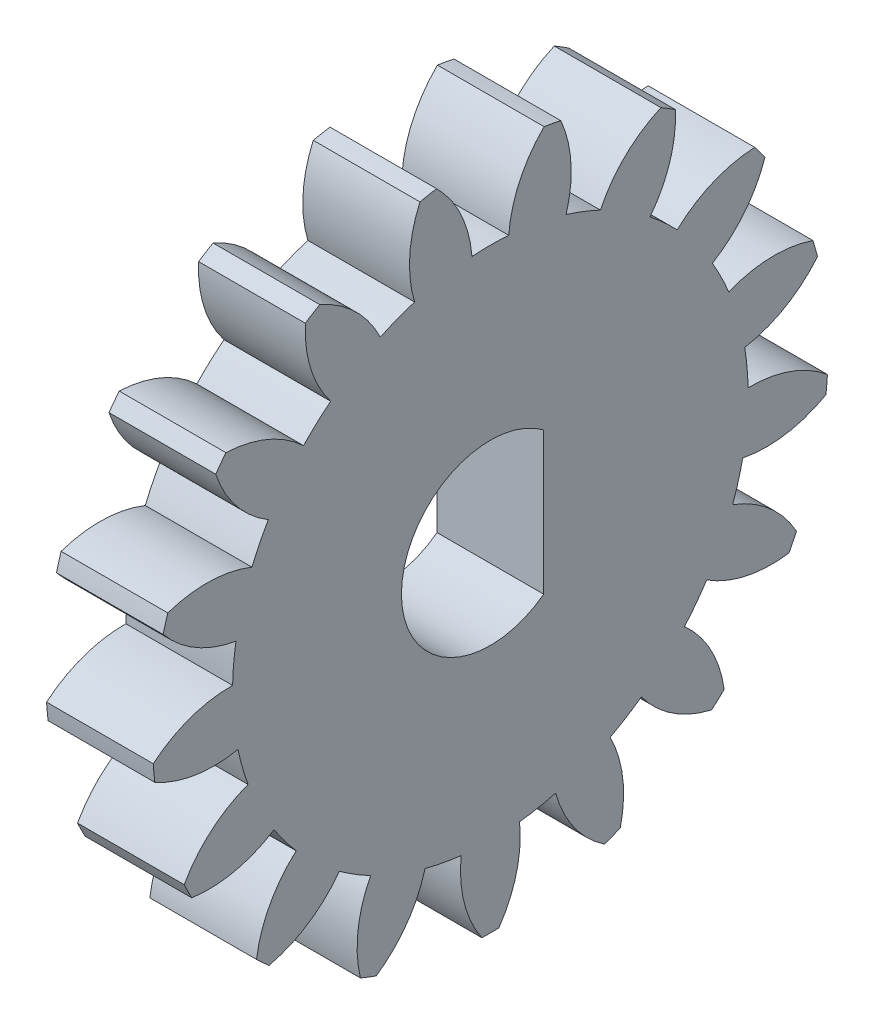
SolidWorks part; units mm, degrees
ref_plane "Plane1" through (0, 0, 0) normal (0, 0, 1) x (1, 0, 0)
ref_plane "Plane2" through (0, 0, 0) normal (0, 1, 0) x (1, 0, 0)
ref_plane "Plane3" through (0, 0, 0) normal (1, 0, 0) x (0, 0, -1)
other "Configuration Table"
sketch "HoldingSke" plane through (0, 0, 0) normal (0, 1, 0) x (1, 0, 0)
  line L0 (0, 0) -> (0.9563, -0.2924)
  line L1 (-15, 0) -> (100, 0) construction
  line L2 (0, 0) -> (-2.1039, 2.3779)
  line L3 (0, 0) -> (-11.863, 4.5341)
  line L4 (0, 0) -> (8.2586, 2.5249)
  line L5 (0, 0) -> (-46.8476, -17.4728)
  line L6 (0, 0) -> (-2.4869, -1.6779)
  line L7 (-2.1039, 2.3779) -> (8.6586, 51.2059)
  line L8 (-76.2, 54.61) -> (-75.3, 54.61)
  line L9 (-71.009, 38.7566) -> (-53.1078, 45.2721)
  line L10 (-76.2, 71.12) -> (104.1128, 71.12)
  line L11 (0, 0) -> (-3, 0)
  line L12 (-76.2, 101.6) -> (-76.162, 101.6)
  line L13 (24.9733, 27.94) -> (52.9518, 28.4284)
  line L14 (24.9733, 27.94) -> (24.9743, 27.94)
  line L15 (24.9733, 27.94) -> (100.4006, 29.5858)
  line L16 (-63.627, -1) -> (-12.827, -1)
  circle A0 centre (0, 0) radius 2.5
  circle A1 centre (0, 0) radius 7.249
  circle A2 centre (0, 0) radius 37.5
  circle A3 centre (0, 0) radius 2.5
  dimension "Num_teeth" = 17
  dimension "Pitch_radius" = 180.3128
  dimension "Width" = 3
  dimension "Thickness" = 3
sketch "BasProSke" plane through (0, 0, 0) normal (0, 1, 0) x (1, 0, 0)
  line L0 (-10, 0) -> (60, 0) construction
  line L1 (0, 0) -> (0, 9.5)
  line L2 (0, 0) -> (3, 0)
  line L3 (3, 0) -> (3, 9.5)
  line L4 (3, 9.5) -> (0, 9.5)
  dimension "Thickness" = 3
  dimension "Diameter" = 19
revolve "Base-Revolve" add sketch "BasProSke" angle 360 about L0
sketch "TooCutSke" plane through (0, 0, 0) normal (1, 0, 0) x (0, 0, -1)
  line L1 (0, 0) -> (0, 107) construction
  line L2 (0, 0) -> (-0.8507, 8.4573) construction
  line L3 (0, 0) -> (-3.1126, 16.6509) construction
  line L4 (-0.8507, 8.4573) -> (-1.5563, 8.3254) construction
  arc A0 (0.5169, 7.2306) -> (-0.5169, 7.2306) centre (0, 0) ccw
  arc A1 (1.5331, 9.4012) -> (-1.5331, 9.4012) centre (0, 0) ccw
  circle A2 centre (0, 0) radius 8.5 construction
  circle A3 centre (0, 0) radius 7.9874 construction
  arc A4 (-0.5169, 7.2306) -> (-1.5331, 9.4012) centre (-3.9066, 6.9668) ccw
  arc A5 (1.5331, 9.4012) -> (0.5169, 7.2306) centre (3.9066, 6.9668) ccw
extrude "ToothCut" cut sketch "TooCutSke" along normal through all
fillet "Breaks" [suppressed] radius 0.02 tangent propagation no
fillet "RootFillets" [suppressed] radius 0.251
pattern_circular "TeethCuts" count 17 every 21.176 about axis through (-10, 0, 0) along (1, 0, 0) of "ToothCut", "RootFillets", "Breaks"
sketch "HubNeaOneSke" plane through (0, 0, 0) normal (-1, 0, 0) x (0, 0, 1)
  circle A0 centre (0, 0) radius 7.249
  dimension "Diameter" = 14.498
extrude "HubNearOne" [suppressed] add sketch "HubNeaOneSke" along normal blind 47.0001
sketch "HubNeaBotSke" plane through (0, 0, 0) normal (-1, 0, 0) x (0, 0, 1)
  circle A0 centre (0, 0) radius 7.249
  dimension "Diameter" = 14.498
extrude "HubNearBoth" [suppressed] add sketch "HubNeaBotSke" along normal blind 23.5
ref_plane "FarPln" through (3, 0, 0) normal (1, 0, 0) x (0, 0, -1)
sketch "HubFarSke" plane through (3, 0, 0) normal (1, 0, 0) x (0, 0, -1)
  circle A0 centre (0, 0) radius 7.249
  dimension "Diameter" = 14.498
extrude "HubFar" [suppressed] add sketch "HubFarSke" along normal blind 23.5
sketch "BorSke" plane through (0, 0, 0) normal (1, 0, 0) x (0, 0, -1)
  circle A0 centre (0, 0) radius 2.5
  dimension "Diameter" = 5
extrude "Bore" cut sketch "BorSke" along normal mid plane 100.0001
sketch "KeySke" plane through (0, 0, 0) normal (1, 0, 0) x (0, 0, -1)
  line L0 (-1, 0) -> (-1, 3.4)
  line L1 (-1, 3.4) -> (1, 3.4)
  line L2 (1, 3.4) -> (1, 0)
  line L3 (0, 0) -> (0, 34) construction
  line L4 (-1, 0) -> (1, 0)
  dimension "Width" = 2
extrude "Keyway" [suppressed] cut sketch "KeySke" along normal mid plane 100.0001
pattern_circular "Keyway2" [suppressed] count 2 every 90 about axis through (-10, 0, 0) along (1, 0, 0) reverse direction yes
sketch "草图1" plane through (3, 0, 0) normal (1, 0, 0) x (0, 0, -1)
  line L0 (1.5, 2) -> (1.5, -2)
  arc A0 (1.5, -2) -> (1.5, 2) centre (0, 0) ccw
  dimension "D1" = 1.5
extrude "凸台-拉伸1" add sketch "草图1" against normal blind 3
equation "' \"Module@HoldingSke\" = 6.35"
equation "' \"Num_teeth@HoldingSke\" = 12"
equation "' \"Ap@HoldingSke\" =  20"
equation "' \"Ap@HoldingSke\" = 20"
equation "' \"Width@HoldingSke\" = 0.5 * 25.4"
equation "' \"Hub_dia@HoldingSke\"= 1 * 25.4"
equation "' \"Hub_dia@HoldingSke\" = 1 * 25.4"
equation "' \"Overall_len@HoldingSke\" = 1.0 * 25.4"
equation "' \"Bore@HoldingSke\" = 0.75 * 25.4"
equation "' \"T_dim@HoldingSke\" = 0.1 * 25.4"
equation "' \"Width@KeySke\" = 0.25 * 25.4"
equation "' \"Show_teeth@HoldingSke\" = 13"
equation "' \"Backlash@HoldingSke\" = 0.009 * 25.4"
equation "' \"Addendum_fac@HoldingSke\" = 1.0"
equation "' \"Dedendum_fac@HoldingSke\" = 1.25"
equation "' \"Dedendum_add@HoldingSke\" = 0.00005 * 25.4"
equation "' \"Clearance_fac@HoldingSke\" = 0.25"
equation "\"Pitch@HoldingSke\" = 1 / \"Module@HoldingSke\""
equation "\"Overcut_dia@TooCutSke\" = (\"Num_teeth@HoldingSke\" + 2 * \"Addendum_fac@HoldingSke\") / \"Pitch@HoldingSke\" + 0.002 * 25.4"
equation "\"Pitch_dia@TooCutSke\" = \"Num_teeth@HoldingSke\" / \"Pitch@HoldingSke\""
equation "\"Base_dia@TooCutSke\" = \"Num_teeth@HoldingSke\" / \"Pitch@HoldingSke\" * cos((\"Ap@HoldingSke\"  * 3.14159265 / 180))"
equation "\"Root_dia@TooCutSke\" = (\"Num_teeth@HoldingSke\" + 2) / \"Pitch@HoldingSke\" - 2 * (\"Addendum_fac@HoldingSke\" + \"Dedendum_fac@HoldingSke\") / \"Pitch@HoldingSke\" - \"Dedendum_add@HoldingSke\" * 2"
equation "\"Half_ang@TooCutSke\" = 180 / \"Num_teeth@HoldingSke\""
equation "\"Half_CT@TooCutSke\" = \"Num_teeth@HoldingSke\" / \"Pitch@HoldingSke\" * sin((3.14159265 / 2 / \"Num_teeth@HoldingSke\")) / 2 - 7 * \"Backlash@HoldingSke\" / 4"
equation "\"Flank_rad@TooCutSke\" = \"Num_teeth@HoldingSke\" / \"Pitch@HoldingSke\" / 5"
equation "\"Radius@RootFillets\" = \"Clearance_fac@HoldingSke\" / \"Pitch@HoldingSke\" + \"Dedendum_add@HoldingSke\""
equation "\"Break_rad@Breaks\" = 0.02 / \"Pitch@HoldingSke\""
equation "\"Thickness@HoldingSke\" = \"Width@HoldingSke\""
equation "\"OAL@HoldingSke\" = \"Thickness@HoldingSke\""
equation "\"MHD@HoldingSke\" = (\"Num_teeth@HoldingSke\" + 2) / \"Pitch@HoldingSke\" - 2 * (\"Addendum_fac@HoldingSke\" + \"Dedendum_fac@HoldingSke\")  / \"Pitch@HoldingSke\" - \"Dedendum_add@HoldingSke\" * 2"
equation "\"MBD@HoldingSke\" = (\"Num_teeth@HoldingSke\" + 2) / \"Pitch@HoldingSke\" - 2 * (\"Addendum_fac@HoldingSke\" + \"Dedendum_fac@HoldingSke\")  / \"Pitch@HoldingSke\" - \"Dedendum_add@HoldingSke\" * 2 - 0.002 * 25.4"
equation "\"MHD@HoldingSke\" = ((sgn( \"MHD@HoldingSke\" - \"Hub_dia@HoldingSke\" )-1)*( \"MHD@HoldingSke\" - \"Hub_dia@HoldingSke\" ))/-2+ \"Hub_dia@HoldingSke\""
equation "\"MBD@HoldingSke\" = ((sgn( \"MBD@HoldingSke\" - \"Bore@HoldingSke\" )-1)*( \"MBD@HoldingSke\" - \"Bore@HoldingSke\" ))/-2+ \"Bore@HoldingSke\""
equation "\"OAL@HoldingSke\" = ((sgn( \"OAL@HoldingSke\" - \"Overall_len@HoldingSke\" )+1)*( \"OAL@HoldingSke\" - \"Overall_len@HoldingSke\" ))/2 + \"Overall_len@HoldingSke\" + 0.000002 * 25.4"
equation "\"Num_teeth@TeethCuts\" = int( \"Show_teeth@HoldingSke\" ) + 1"
equation "\"Num_teeth@TeethCuts\" = ((sgn( \"Num_teeth@TeethCuts\" - \"Num_teeth@HoldingSke\" )-1)*( \"Num_teeth@TeethCuts\" - \"Num_teeth@HoldingSke\" ))/-2+ \"Num_teeth@HoldingSke\""
equation "\"Num_teeth@TeethCuts\" = ((sgn( \"Num_teeth@TeethCuts\" - 2.0)+1)*( \"Num_teeth@TeethCuts\" - 2.0))/2 +2.0"
equation "\"Angle@TeethCuts\" = 360.0 / \"Num_teeth@HoldingSke\""
equation "\"Diameter@BasProSke\" = (\"Num_teeth@HoldingSke\" + 2 * \"Addendum_fac@HoldingSke\") / \"Pitch@HoldingSke\""
equation "\"Thickness@BasProSke\"  = \"Thickness@HoldingSke\""
equation "' \"Fillet_rad@BasProSke\" =  \"Thickness@HoldingSke\" * 0.05"
equation "' \"Fillet_rad@BasProSke\" = \"Thickness@HoldingSke\" * 0.05"
equation "\"MHD@HoldingSke\" = ((sgn( \"MHD@HoldingSke\" - \"Root_dia@TooCutSke\" )-1)*( \"MHD@HoldingSke\" - \"Root_dia@TooCutSke\" ))/-2+ \"Root_dia@TooCutSke\""
equation "\"Diameter@HubNeaOneSke\" = \"MHD@HoldingSke\""
equation "\"Length@HubNearOne\" = \"OAL@HoldingSke\" - \"Thickness@BasProSke\""
equation "\"Diameter@HubNeaBotSke\" = \"MHD@HoldingSke\""
equation "\"Length@HubNearBoth\" = ( \"OAL@HoldingSke\" - \"Thickness@BasProSke\" ) / 2.0"
equation "\"Thickness@FarPln\" = \"Thickness@BasProSke\""
equation "\"Diameter@HubFarSke\" = \"MHD@HoldingSke\""
equation "\"Length@HubFar\" = ( \"OAL@HoldingSke\" - \"Thickness@BasProSke\" ) / 2.0"
equation "\"Diameter@BorSke\" = \"MBD@HoldingSke\""
equation "\"D1@Bore\" = \"OAL@HoldingSke\" * 2.0"
equation "\"D1@Keyway\" = \"OAL@HoldingSke\" * 2.0"
equation "\"Offset@KeySke\" = \"T_dim@HoldingSke\" + \"MBD@HoldingSke\" / 2.0"
